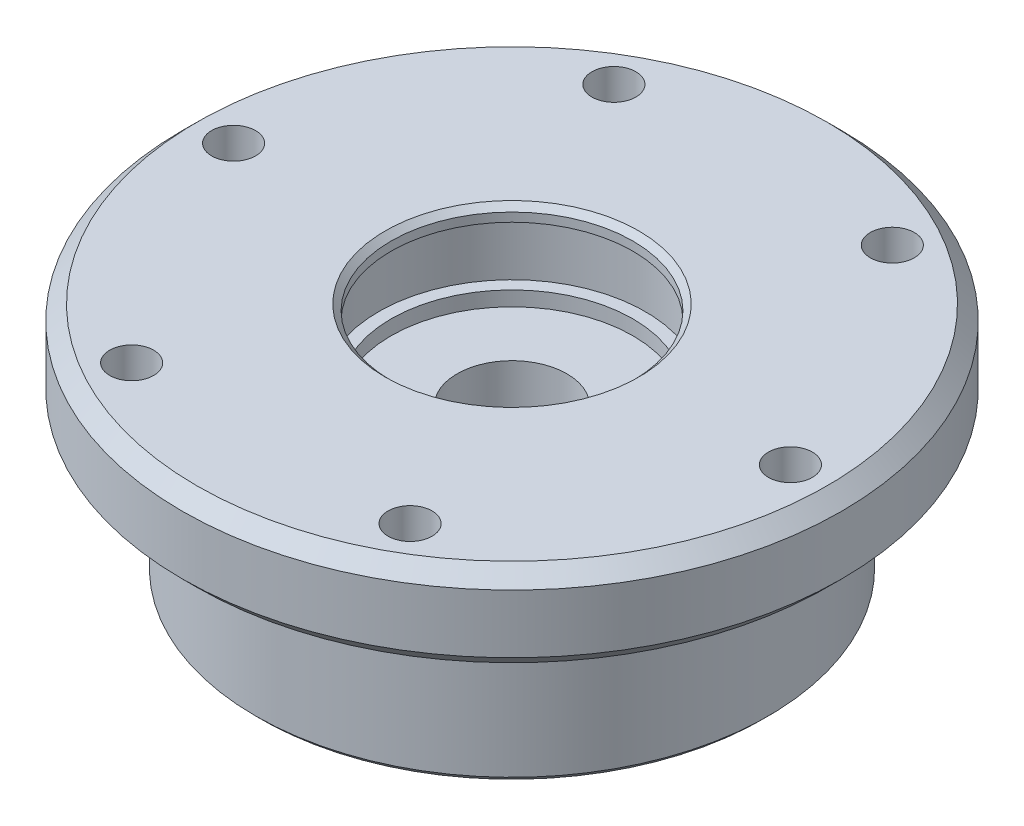
SolidWorks part; units mm, degrees
ref_plane "Front Plane" through (0, 0, 0) normal (0, 0, 1) x (1, 0, 0)
ref_plane "Top Plane" through (0, 0, 0) normal (0, 1, 0) x (1, 0, 0)
ref_plane "Right Plane" through (0, 0, 0) normal (1, 0, 0) x (0, 0, -1)
sketch "Sketch1" plane through (0, 0, 0) normal (0, 1, 0) x (1, 0, 0)
  circle A0 centre (0, 0) radius 19 construction
  circle A1 centre (19, 0) radius 1.5
  circle A2 centre (9.5, -16.4545) radius 1.5
  circle A3 centre (-9.5, -16.4545) radius 1.5
  circle A4 centre (-19, 0) radius 1.5
  circle A5 centre (-9.5, 16.4545) radius 1.5
  circle A6 centre (9.5, 16.4545) radius 1.5
  circle A7 centre (0, 0) radius 22.5
  circle A8 centre (0, 0) radius 8.25
  point P17 (0, 0)
  dimension "D1" = 38
  dimension "D2" = 3
  dimension "D5" = 16.5
  dimension "D4" = 3.5
  dimension "D3" = 6
extrude "Boss-Extrude1" add sketch "Sketch1" along normal mid plane 6
sketch "Sketch2" plane through (0, 0, 0) normal (0, 1, 0) x (1, 0, 0)
  circle A0 centre (0, 0) radius 9.1
  dimension "D1" = 18.2
extrude "Cut-Extrude1" cut sketch "Sketch2" against normal mid plane 4
sketch "Sketch3" plane through (0, -3, 0) normal (0, 1, 0) x (1, 0, 0)
  circle A0 centre (0, 0) radius 17.5
  circle A1 centre (0, 0) radius 20.5
  circle A2 centre (9.5, 16.4545) radius 1.5 construction
extrude "Boss-Extrude2" add sketch "Sketch3" along normal blind 1
sketch "Sketch4" plane through (0, -3, 0) normal (0, -1, 0) x (1, 0, 0)
  circle A0 centre (0, 0) radius 17.5
  circle A2 centre (0, 0) radius 3.75
  dimension "D1" = 35
  dimension "D2" = 7.5
extrude "Boss-Extrude3" add sketch "Sketch4" along normal blind 10
sketch "Sketch5" plane through (0, -3, 0) normal (0, -1, 0) x (1, 0, 0)
  circle A0 centre (0, 0) radius 19
  circle A1 centre (0, 0) radius 17.5 construction
  circle A2 centre (0, 0) radius 17.5
  dimension "D1" = 1.5
extrude "Boss-Extrude4" add sketch "Sketch5" along normal blind 0.5
chamfer "Chamfer1" distance 1 angle 45 2 edges at (0, -3, 22.5) (0, 3, 22.5)
chamfer "Chamfer2" [suppressed] distance 0.4 angle 45
chamfer "Chamfer3" distance 0.4 angle 45 1 edges at (0, 3, 8.25)
sketch "Sketch6" plane through (0, -13, 0) normal (0, -1, 0) x (1, 0, 0)
  circle A0 centre (0, 0) radius 7.5 construction
  circle A1 centre (7.5, 0) radius 2.35
  circle A2 centre (0, 7.5) radius 2.35
  circle A3 centre (-7.5, 0) radius 2.35
  circle A4 centre (0, -7.5) radius 2.35
  dimension "D1" = 15
  dimension "D2" = 4.7
extrude "Cut-Extrude2" cut sketch "Sketch6" against normal blind 4
sketch "Sketch7" plane through (0, -13, 0) normal (0, -1, 0) x (1, 0, 0)
  circle A0 centre (0, 7.5) radius 1.75
  circle A1 centre (7.5, 0) radius 1.75
  circle A2 centre (0, -7.5) radius 1.75
  circle A3 centre (-7.5, 0) radius 1.75
  dimension "D1" = 3.5
extrude "Cut-Extrude3" cut sketch "Sketch7" against normal blind 8
chamfer "Chamfer4" distance 0.4 angle 45 1 edges at (0, -13, -17.5)
equation "\"RotorRadius\"= 25mm"
equation "\"Eccentricity\"= 1.00mm"
equation "\"RollerRadius\"= 1.5mm"
equation "\"GearRatio\"= 20"
equation "\"RollerCount\"=\"GearRatio\" + 1"
equation "\"RotorThickness\"= 6mm"
equation "\"OutputRollerRadius\"= 1.5mm"
equation "\"OutputRollerCount\"= 6"
equation "\"OutputRollerHoleCircleRadius\"=\"RotorRadius\"- 4 * \"OutputRollerRadius\""
equation "\"RotorGap\"= 0.5mm"
equation "\"D1@Sketch1\"=2*\"OutputRollerHoleCircleRadius\""
equation "\"D2@Sketch1\"=\"OutputRollerRadius\"*2"
equation "\"D1@Boss-Extrude1\"=\"RotorThickness\""
